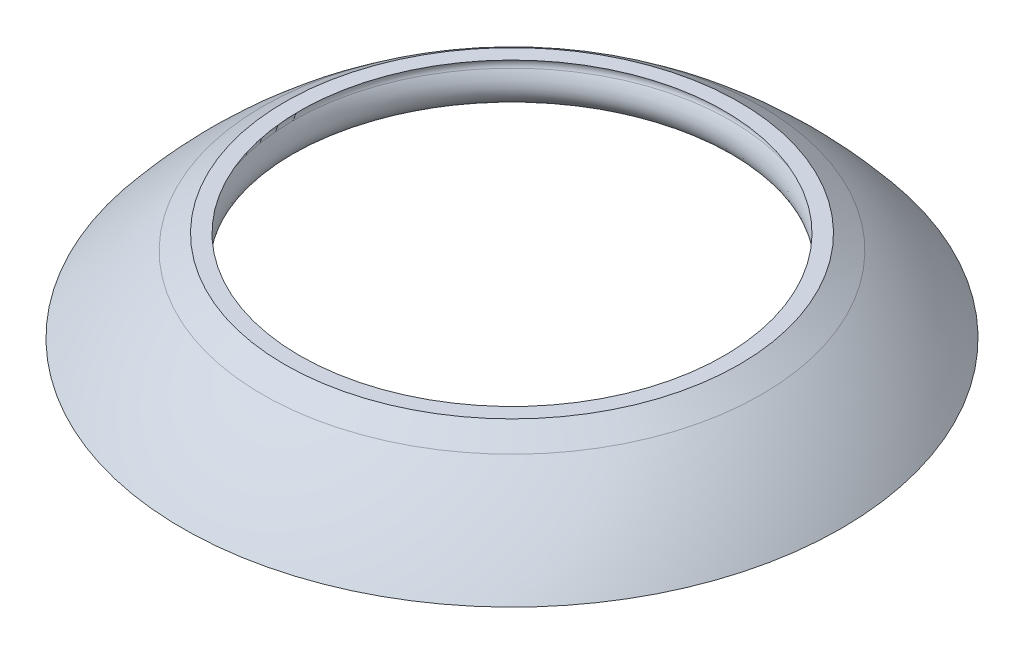
SolidWorks part; units mm, degrees
ref_plane "Front" through (0, 0, 0) normal (0, 0, 1) x (1, 0, 0)
ref_plane "Top" through (0, 0, 0) normal (0, 1, 0) x (1, 0, 0)
ref_plane "Right" through (0, 0, 0) normal (1, 0, 0) x (0, 0, -1)
sketch "Sketch6"
  line L0 (0, 4.4657) -> (0, -0.4998) construction
  line L1 (0, -16.2) -> (0, -60.6715) construction
  line L5 (5.4929, 4.08) -> (5.8861, 4.08)
  line L6 (5.8861, 4.08) -> (6.4597, 3.6926)
  line L9 (0, -16.2) -> (0, -16.52)
  line L11 (5.4929, 4.08) -> (5.8861, 4.08)
  arc A2 (5.6645, 3.7773) -> (5.4929, 4.08) centre (5.4929, 3.88) ccw
  arc A12 (8.5323, 1.73) -> (6.4597, 3.6926) centre (0, -5.2049) ccw
  spline S1 degree 3 poles (5.6645, 3.7773) (5.528, 3.5492) (5.4172, 2.8544) (6.9838, 2.5219) (8.0807, 1.9174) (8.5323, 1.73) knots 0.065551 0.065551 0.065551 0.065551 0.226972 0.688222 1 1 1 1
  dimension "D19" = 10.9951
  dimension "D2" = 0.2
sketch "Sketch6<7>" plane through (0, 0, 0) normal (0, 0, 1) x (1, 0, 0) same geometry as "Sketch6"
revolve "iris" add sketch "Sketch6" angle 360 about L0
revolve "ciliary body" add sketch "Sketch6" angle 360 about L0
